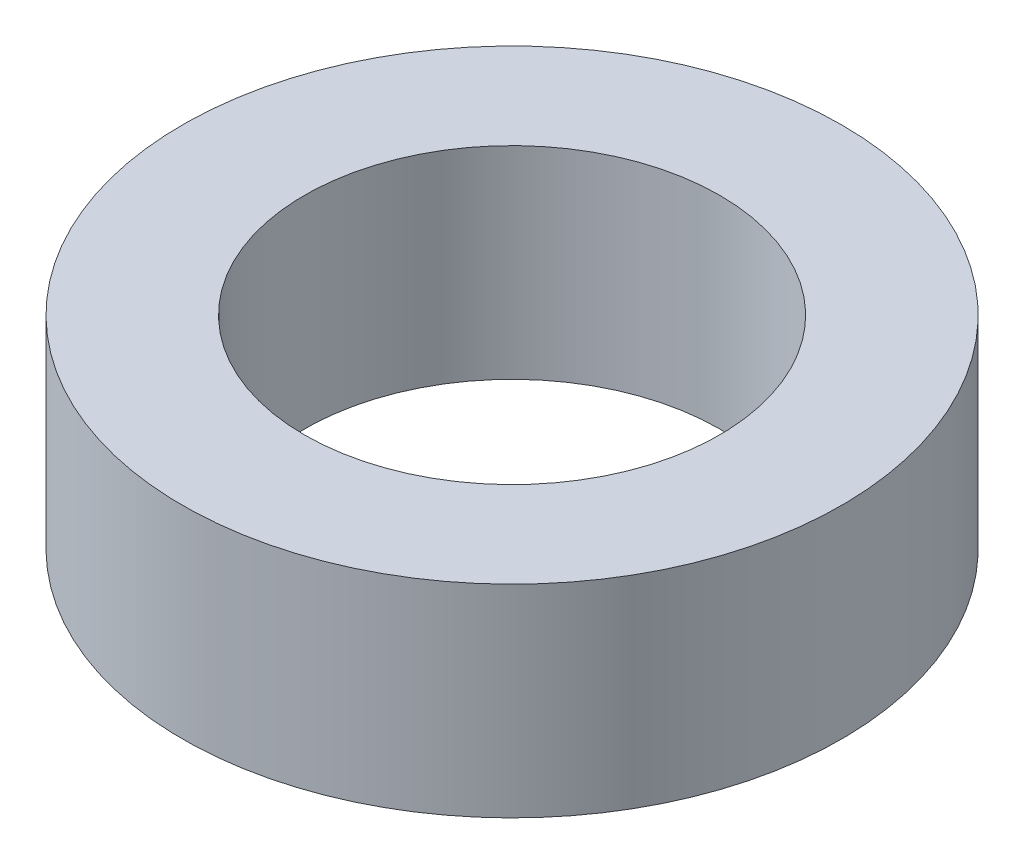
SolidWorks part; units mm, degrees
ref_plane "Front Plane" through (0, 0, 0) normal (0, 0, 1) x (1, 0, 0)
ref_plane "Top Plane" through (0, 0, 0) normal (0, 1, 0) x (1, 0, 0)
ref_plane "Right Plane" through (0, 0, 0) normal (1, 0, 0) x (0, 0, -1)
sketch "Sketch1" plane through (0, 0, 0) normal (0, 1, 0) x (1, 0, 0)
  circle A0 centre (0, 0) radius 6.35
  dimension "D1" = 12.7
extrude "Boss-Extrude1" add sketch "Sketch1" along normal blind 3.9
sketch "Sketch2" plane through (0, 3.9, 0) normal (0, 1, 0) x (1, 0, 0)
  circle A0 centre (0, 0) radius 4
  dimension "D1" = 8
sketch "Sketch3" plane through (0, 3.9, 0) normal (0, 1, 0) x (1, 0, 0)
  circle A0 centre (0, 0) radius 4
  dimension "D1" = 8
extrude "Cut-Extrude2" cut sketch "Sketch3" against normal through all
